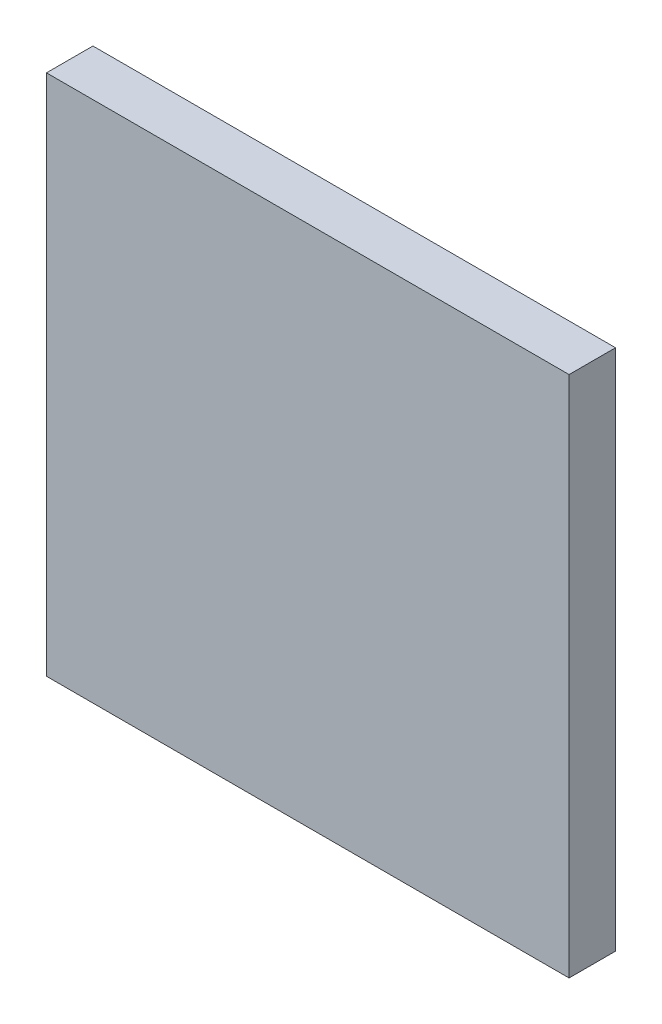
SolidWorks part; units mm, degrees
ref_plane "前视基准面" through (0, 0, 0) normal (0, 0, 1) x (1, 0, 0)
ref_plane "上视基准面" through (0, 0, 0) normal (0, 1, 0) x (1, 0, 0)
ref_plane "右视基准面" through (0, 0, 0) normal (1, 0, 0) x (0, 0, -1)
sketch "草图1" plane through (0, 0, 0) normal (0, 0, 1) x (1, 0, 0)
  line L1 (0, 0) -> (90, 0)
  line L2 (0, 0) -> (0, 90)
  line L3 (0, 90) -> (90, 90)
  line L4 (90, 0) -> (90, 90)
  dimension "D1" = 90
  dimension "D2" = 90
extrude "凸台-拉伸1" add sketch "草图1" along normal blind 8
